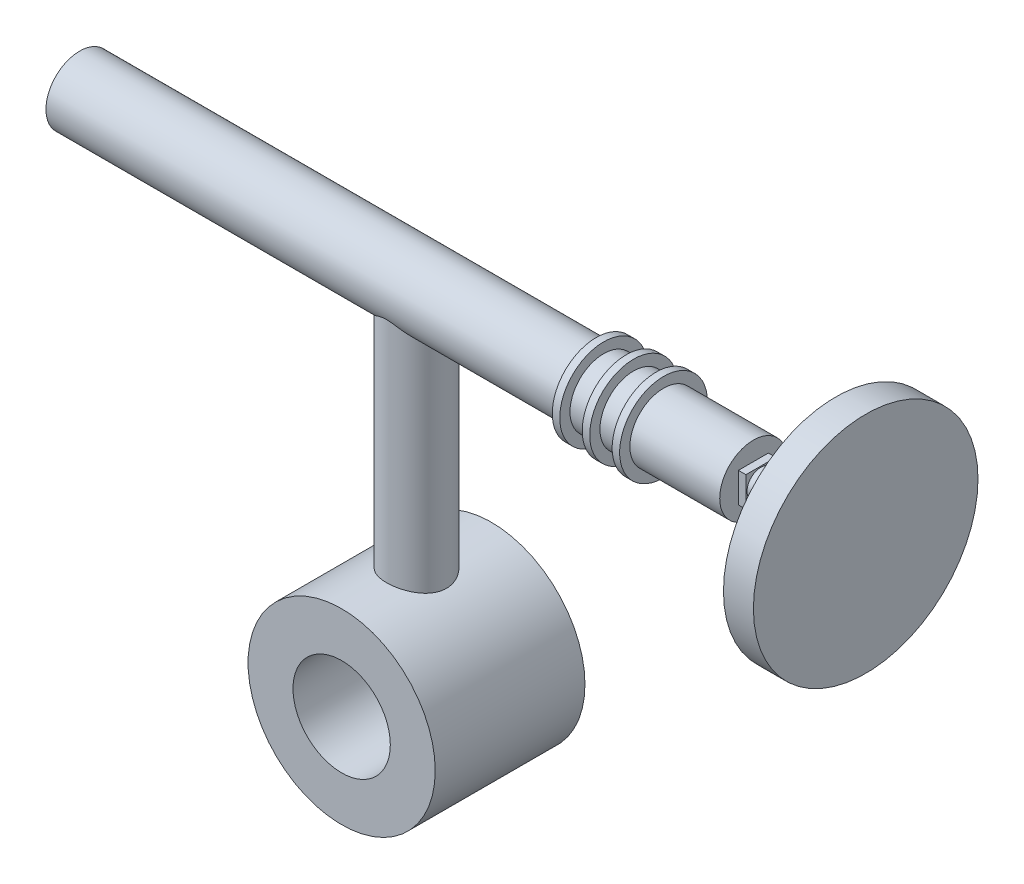
SolidWorks part; units mm, degrees
material "Pure Gold"
ref_plane "Front Plane" through (0, 0, 0) normal (0, 0, 1) x (1, 0, 0)
ref_plane "Top Plane" through (0, 0, 0) normal (0, 1, 0) x (1, 0, 0)
ref_plane "Right Plane" through (0, 0, 0) normal (1, 0, 0) x (0, 0, -1)
other "Configuration Table"
sketch "Sketch2" plane through (0, 0, 0) normal (0, 0, 1) x (1, 0, 0)
  circle A0 centre (0, 0) radius 6.25
  dimension "D1" = 12.5
extrude "Extrude1" add sketch "Sketch2" along normal mid plane 10
sketch "Sketch3" plane through (0, 0, 0) normal (0, 1, 0) x (-1, 0, 0)
  circle A0 centre (0, 0) radius 2
  dimension "D1" = 4
extrude "Extrude2" add sketch "Sketch3" along normal blind 22.5
sketch "Sketch4" plane through (0, 0, 0) normal (1, 0, 0) x (0, 0, -1)
  line L0 (2, 22.5) -> (-2, 22.5) construction
  circle A0 centre (0, 22.5) radius 2.25
  dimension "D1" = 4.5
extrude "Extrude3" add sketch "Sketch4" along normal blind 22.5 and the other way blind 22.5
ref_plane "Plane3" through (12, 0, 0) normal (1, 0, 0) x (0, 0, -1)
sketch "Sketch5" plane through (12, 0, 0) normal (1, 0, 0) x (0, 0, -1)
  circle A0 centre (0, 22.5) radius 2.9338
extrude "Extrude4" add sketch "Sketch5" along normal blind 0.5
sketch "Sketch8" plane through (0, 0, 0) normal (0, 1, 0) x (-1, 0, 0)
  line L0 (-124.0656, -12.0237) -> (-134.7052, -12.0237)
pattern_linear "LPattern1" count 3 spacing 2 along (1, 0, 0) of "Extrude4"
sketch "Sketch9" plane through (22.5, 0, 0) normal (1, 0, 0) x (0, 0, -1)
  line L0 (-1, 21.5) -> (1, 23.5) construction
  line L1 (-1, 23.5) -> (1, 23.5)
  line L2 (-1, 23.5) -> (-1, 21.5)
  line L3 (-1, 21.5) -> (1, 21.5)
  line L4 (1, 23.5) -> (1, 21.5)
  circle A1 centre (0, 22.5) radius 2.25 construction
  point P6 (0, 22.5)
  dimension "D1" = 2
  dimension "D2" = 2
extrude "Extrude6" add sketch "Sketch9" along normal blind 0.5
sketch "Sketch7" plane through (0, 0, 5) normal (0, 0, 1) x (1, 0, 0)
  circle A0 centre (0, 0) radius 3.25
  dimension "D1" = 6.5
extrude "Cut-Extrude1" cut sketch "Sketch7" against normal through all
sketch "Sketch6" plane through (23, 0, 0) normal (1, 0, 0) x (0, 0, -1)
  circle A0 centre (0, 22.5) radius 0.925
  dimension "D1" = 1.85
extrude "Extrude7" add sketch "Sketch6" along normal blind 5
sketch "Sketch10" plane through (28, 0, 0) normal (1, 0, 0) x (0, 0, -1)
  circle A0 centre (0, 22.5) radius 7.5
  dimension "D1" = 15
extrude "Extrude8" add sketch "Sketch10" along normal blind 2
